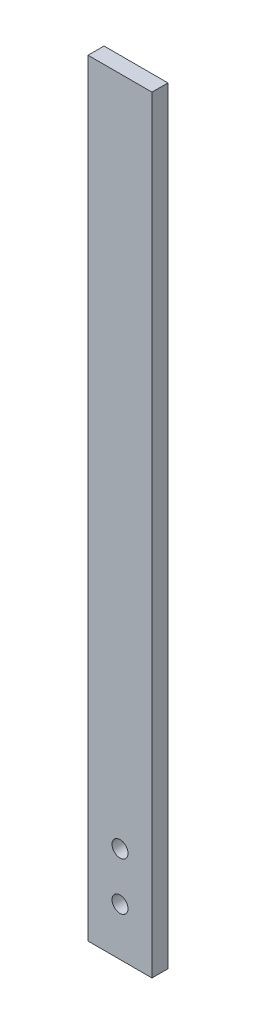
SolidWorks part; units mm, degrees
material "6061 Alloy"
ref_plane "Front Plane" through (0, 0, 0) normal (0, 0, 1) x (1, 0, 0)
ref_plane "Top Plane" through (0, 0, 0) normal (0, 1, 0) x (1, 0, 0)
ref_plane "Right Plane" through (0, 0, 0) normal (1, 0, 0) x (0, 0, -1)
sketch "Sketch2" plane through (0, 0, 0) normal (0, 1, 0) x (1, 0, 0)
  line L1 (0, 0) -> (25.4, 0)
  line L2 (0, 0) -> (0, 6.35)
  line L3 (0, 6.35) -> (25.4, 6.35)
  line L4 (25.4, 0) -> (25.4, 6.35)
  line L5 (0, 0) -> (20.6375, 0)
  line L6 (0, 0) -> (0, 1.5875)
  dimension "D1" = 25.4
  dimension "D2" = 6.35
extrude "Boss-Extrude1" add sketch "Sketch2" along normal blind 304.8 contours L1 L4 L3 L2 region at (12.7, 0, -3.175)
sketch "Sketch3" plane through (0, 0, 0) normal (0, 0, 1) x (1, 0, 0)
  line L0 (0, 0) -> (25.4, 0) construction
  line L1 (0, 304.8) -> (0, 0) construction
  circle A0 centre (12.7, 19.05) radius 3.175
  circle A1 centre (12.7, 38.1) radius 3.175
  point P2 (12.7, 0)
  dimension "D1" = 19.05
  dimension "D3" = 38.1
  dimension "D2" = 12.7
  dimension "D4" = 12.7
extrude "Cut-Extrude1" cut sketch "Sketch3" against normal blind 48.514
